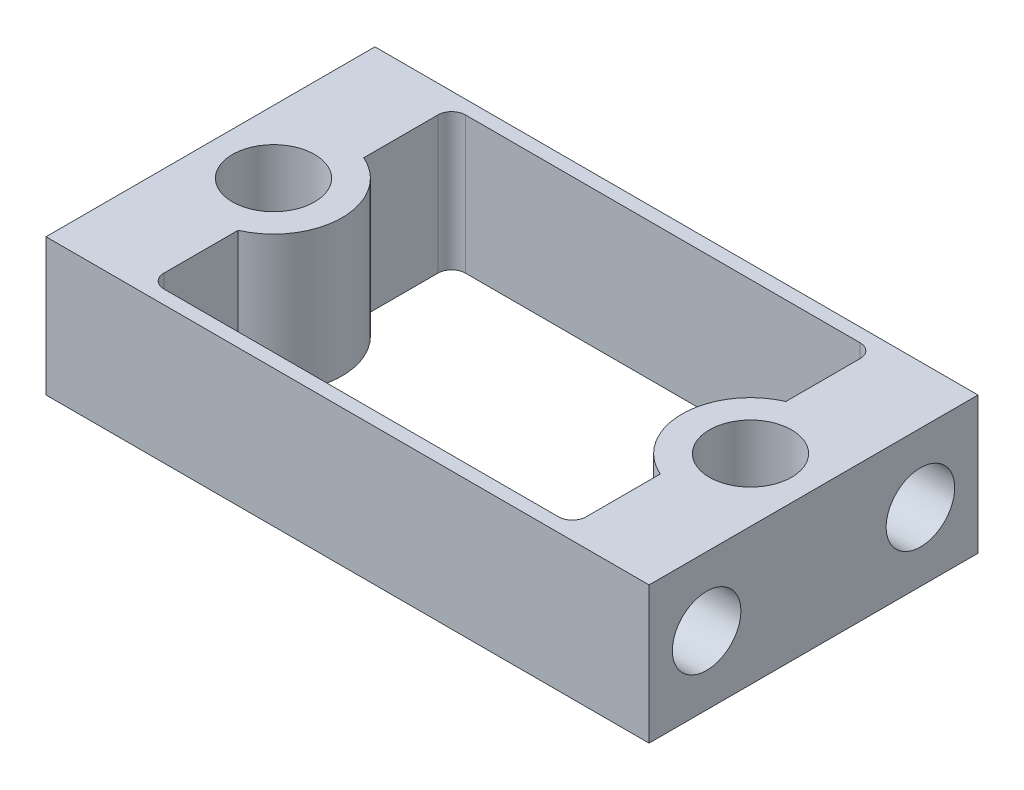
SolidWorks part; units mm, degrees
ref_plane "Front Plane" through (0, 0, 0) normal (0, 0, 1) x (1, 0, 0)
ref_plane "Top Plane" through (0, 0, 0) normal (0, 1, 0) x (1, 0, 0)
ref_plane "Right Plane" through (0, 0, 0) normal (1, 0, 0) x (0, 0, -1)
sketch "Sketch1" plane through (0, 0, 0) normal (0, 1, 0) x (1, 0, 0)
  line L1 (-11, 6) -> (11, 6)
  line L2 (-11, 6) -> (-11, -6)
  line L3 (-11, -6) -> (11, -6)
  line L4 (11, 6) -> (11, -6)
  line L5 (-11, 6) -> (11, -6) construction
  line L6 (-11, -6) -> (11, 6) construction
  point P0 (0, 0)
  dimension "D1" = 22
  dimension "D2" = 12
extrude "Boss-Extrude1" add sketch "Sketch1" along normal blind 5
sketch "Sketch2" plane through (0, 5, 0) normal (0, 1, 0) x (1, 0, 0)
  line L0 (8.7, -3.7) -> (8.7, -1.5) construction
  line L2 (-8.7, 3.7) -> (-8.7, 1.5) construction
  line L4 (11, -6) -> (11, 6)
  line L5 (11, 6) -> (-11, 6)
  line L6 (-11, 6) -> (-11, -6)
  line L7 (-11, -6) -> (11, -6)
  line L8 (11, -6) -> (11, 6) construction
  line L9 (11, 6) -> (-11, 6) construction
  line L10 (-11, 6) -> (-11, -6) construction
  line L11 (-11, -6) -> (11, -6) construction
  line L12 (-8.7, -1.5) -> (-8.7, -3.7) construction
  line L13 (-8.7, 3.7) -> (-8.7, -3.7) construction
  line L14 (8.7, 1.5) -> (8.7, 3.7) construction
  line L15 (8.7, -3.7) -> (8.7, 3.7) construction
  line L16 (7.7, -5.5) -> (7.7, -2.2913)
  line L18 (-7.7, -2.2913) -> (-7.7, -5.5)
  line L19 (-7.7, 5.5) -> (-7.7, 2.2913)
  line L21 (7.7, 2.2913) -> (7.7, 5.5)
  line L22 (-7.7, 5.5) -> (7.7, 5.5)
  line L23 (8.7, 3.7) -> (-8.7, 3.7) construction
  line L24 (-7.7, -5.5) -> (7.7, -5.5)
  line L25 (-8.7, -3.7) -> (8.7, -3.7) construction
  line L26 (-11, -6) -> (11, -6) construction
  arc A0 (-8.7, -1.5) -> (-8.7, 1.5) centre (-8.7, 0) ccw construction
  arc A1 (8.7, 1.5) -> (8.7, -1.5) centre (8.7, 0) ccw construction
  arc A2 (7.7, 2.2913) -> (7.7, -2.2913) centre (8.7, 0) ccw
  arc A3 (-7.7, -2.2913) -> (-7.7, 2.2913) centre (-8.7, 0) ccw
  point P11 (-7.2, 0)
  point P15 (-11, 0)
  dimension "D3" = 3
  dimension "D4" = 17.4
  dimension "D9" = 1
  dimension "D10" = 1
  dimension "D2" = 17.4
  dimension "D5" = 1
  dimension "D6" = 1
  dimension "D7" = 0.5
  dimension "D8" = 0.5
  dimension "D1" = 0
hole_wizard "M3 Clearance Hole1" positions "Sketch3" profile "Sketch4" hole size "M3" standard "ANSI Metric" end condition through all
sketch "Sketch3" plane through (0, 5, 0) normal (0, 1, 0) x (1, 0, 0)
  point P0 (-8.7, 0)
  point P3 (8.7, 0)
sketch "Sketch4" plane through (-8.7, 5, 0) normal (1, 0, 0) x (0, 0, 1)
  line L0 (0, 0) -> (0, 5)
  line L1 (0, 5) -> (1.5, 5)
  line L2 (1.5, 5) -> (1.5, 0)
  line L5 (1.5, 0) -> (0, 0)
  line L11 (0, -6.35) -> (0, 107.95) construction
  dimension "Thru Hole Dia." = 3
  dimension "Thru Hole Depth" = 5
extrude "Cut-Extrude1" cut sketch "Sketch2" against normal through all
sketch "Sketch5" plane through (11, 0, 0) normal (1, 0, 0) x (0, 0, -1)
  line L0 (-3.9, 2.5) -> (3.9, 2.5) construction
  line L1 (-6, 5) -> (6, 5) construction
  line L2 (6, 5) -> (6, 0) construction
  point P0 (-3.9, 2.5)
  point P1 (3.9, 2.5)
  point P6 (0, 5)
  point P7 (0, 2.5)
  point P11 (6, 2.5)
  dimension "D1" = 7.8
hole_wizard "M3x0.5 Tapped Hole2" positions "Sketch6" profile "Sketch7" tap size "M3x0.5" standard "ANSI Metric" end condition up to next
sketch "Sketch6" plane through (11, 0, 0) normal (1, 0, 0) x (0, 0, -1)
  point P0 (-3.9, 2.5)
  point P3 (3.9, 2.5)
sketch "Sketch7" plane through (11, 2.5, 3.9) normal (0, 1, 0) x (0, 0, -1)
  line L0 (0, 0) -> (0, 3.3)
  line L1 (0, 3.3) -> (1.25, 3.3)
  line L2 (1.25, 3.3) -> (1.25, 0)
  line L5 (1.25, 0) -> (0, 0)
  line L11 (0, -6.35) -> (0, 107.95) construction
  dimension "Thru Tap Drill Dia." = 2.5
  dimension "Thru Tap Drill Depth" = 3.3
cosmetic thread "Hole Thread3" parameters "D2"=3
cosmetic thread "Hole Thread4" parameters "D2"=3
fillet "Fillet1" radius 0.5 4 edges at (7.7, 2.5, 5.5) (7.7, 2.5, -5.5) (-7.7, 2.5, -5.5) (-7.7, 2.5, 5.5)
